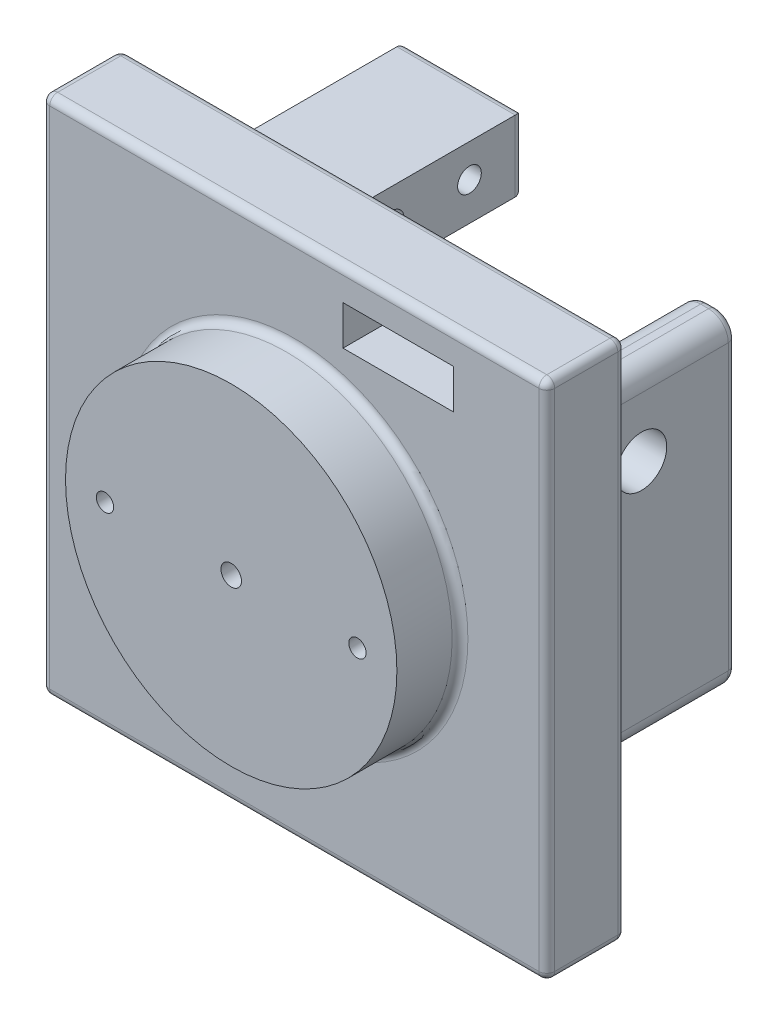
SolidWorks part; units mm, degrees
ref_plane "Front Plane" through (0, 0, 0) normal (0, 0, 1) x (1, 0, 0)
ref_plane "Top Plane" through (0, 0, 0) normal (0, 1, 0) x (1, 0, 0)
ref_plane "Right Plane" through (0, 0, 0) normal (1, 0, 0) x (0, 0, -1)
sketch "Sketch1" plane through (0, 0, 0) normal (0, 0, 1) x (1, 0, 0)
  circle A0 centre (0, 0) radius 21
  dimension "D1" = 42
extrude "Boss-Extrude1" add sketch "Sketch1" along normal blind 8
sketch "Sketch2" plane through (0, 0, 0) normal (0, 0, -1) x (-1, 0, 0)
  circle A0 centre (0, 0) radius 1.3
  dimension "D1" = 2.6
extrude "Cut-Extrude1" cut sketch "Sketch2" against normal through all both and the other way through all contours A0
sketch "Sketch4" plane through (0, 0, 0) normal (0, 0, -1) x (-1, 0, 0)
  circle A0 centre (16, 0) radius 1.1
  dimension "D1" = 16
  dimension "D3" = 2.2
  dimension "D2" = 0
sketch "Sketch5" plane through (0, 0, 0) normal (0, 0, -1) x (-1, 0, 0)
  circle A0 centre (-16, 0) radius 1.1
  dimension "D1" = 16
  dimension "D3" = 2.2
  dimension "D2" = 32
extrude "Cut-Extrude2" cut sketch "Sketch4" against normal blind 10
extrude "Cut-Extrude3" cut sketch "Sketch5" against normal blind 10
sketch "Sketch11" plane through (0, 0, 0) normal (0, 0, -1) x (-1, 0, 0)
  line L1 (-32, 33) -> (32, 33)
  line L2 (-32, 33) -> (-32, -33)
  line L3 (-32, -33) -> (32, -33)
  line L4 (32, 33) -> (32, -33)
  line L5 (-32, 33) -> (32, -33) construction
  line L6 (-32, -33) -> (32, 33) construction
  point P0 (0, 0)
  dimension "D1" = 64
  dimension "D2" = 66
extrude "Boss-Extrude3" add sketch "Sketch11" along normal blind 10
sketch "Sketch17" plane through (0, 0, 0) normal (0, 0, 1) x (1, 0, 0)
  circle A0 centre (0, 0) radius 1.3
  dimension "D1" = 2.6
extrude "Cut-Extrude8" cut sketch "Sketch17" against normal blind 10
sketch "Sketch12" plane through (0, 0, -10) normal (0, 0, -1) x (-1, 0, 0)
  line L0 (32, -33) -> (32, 33) construction
  line L1 (18, -29.5) -> (3, -29.5)
  line L2 (18, -29.5) -> (18, -20.5)
  line L3 (18, -20.5) -> (3, -20.5)
  line L4 (3, -29.5) -> (3, -20.5)
  line L5 (18, -29.5) -> (3, -20.5) construction
  line L6 (18, -20.5) -> (3, -29.5) construction
  line L7 (18, 20.5) -> (3, 20.5)
  line L8 (18, 20.5) -> (18, 29.5)
  line L9 (18, 29.5) -> (3, 29.5)
  line L10 (3, 20.5) -> (3, 29.5)
  line L11 (18, 20.5) -> (3, 29.5) construction
  line L12 (18, 29.5) -> (3, 20.5) construction
  line L13 (32, 33) -> (-32, 33) construction
  line L14 (-32, -33) -> (32, -33) construction
  point P0 (10.5, -25)
  point P5 (10.5, 25)
  dimension "D1" = 41
  dimension "D2" = 3.5
  dimension "D3" = 3.5
  dimension "D4" = 9
  dimension "D5" = 15
  dimension "D6" = 15
  dimension "D7" = 14
  dimension "D8" = 14
extrude "Boss-Extrude4" add sketch "Sketch12" along normal blind 22
sketch "Sketch13" plane through (-18, 0, 0) normal (-1, 0, 0) x (0, 0, 1)
  line L0 (-32, -29.5) -> (-32, -20.5) construction
  line L1 (-32, -29.5) -> (-10, -29.5) construction
  line L2 (-32, 29.5) -> (-10, 29.5) construction
  line L3 (-32, 20.5) -> (-32, 29.5) construction
  circle A0 centre (-25.2, -25.3) radius 1.5
  circle A1 centre (-15.4, -25.3) radius 1.5
  circle A2 centre (-25.2, 25.3) radius 1.5
  circle A3 centre (-15.4, 25.3) radius 1.5
  dimension "D2" = 3
  dimension "D3" = 3
  dimension "D7" = 3
  dimension "D8" = 3
  dimension "D1" = 9.8
  dimension "D4" = 4.2
  dimension "D5" = 4.2
  dimension "D6" = 6.8
  dimension "D9" = 9.8
  dimension "D10" = 4.2
  dimension "D11" = 6.8
  dimension "D12" = 4.2
extrude "Cut-Extrude4" cut sketch "Sketch13" against normal blind 21
sketch "Sketch14" plane through (0, 0, -10) normal (0, 0, -1) x (-1, 0, 0)
  line L0 (3, 20.5) -> (18, 20.5) construction
  line L1 (-24, 20.5) -> (-18, 20.5)
  line L2 (-24, 20.5) -> (-24, -20.5)
  line L3 (-24, -20.5) -> (-18, -20.5)
  line L4 (-18, 20.5) -> (-18, -20.5)
  line L5 (-24, 20.5) -> (-18, -20.5) construction
  line L6 (-24, -20.5) -> (-18, 20.5) construction
  line L7 (18, -20.5) -> (3, -20.5) construction
  point P0 (-21, 0)
  dimension "D1" = 36
  dimension "D2" = 0
  dimension "D3" = 0
  dimension "D4" = 6
extrude "Boss-Extrude5" add sketch "Sketch14" along normal blind 22
sketch "Sketch15" plane through (18, 0, 0) normal (-1, 0, 0) x (0, 0, 1)
  line L0 (-10, -20.5) -> (-10, 20.5) construction
  line L2 (-32, 20.5) -> (-10, 20.5) construction
  circle A0 centre (-20, 10.5) radius 3.2
  dimension "D1" = 10
  dimension "D3" = 6.4
  dimension "D2" = 10
extrude "Cut-Extrude6" cut sketch "Sketch15" against normal blind 22
fillet "Fillet12" radius 1 13 edges at (32, 0, 0) (21, 0, 0) (32, 33, -5) (0, 33, 0) (32, -33, -5) (0, -33, 0) (-32, -33, -5) (-32, 33, -5) (-32, 0, 0) (0, -33, -10) (32, 0, -10) (0, 33, -10) (-32, 0, -10)
fillet "Fillet13" radius 1 12 edges at (21, -20.5, -32) (24, 0, -32) (21, 20.5, -32) (18, 0, -32) (-10.5, 29.5, -32) (-18, 25, -32) (-10.5, 20.5, -32) (-3, 25, -32) (-10.5, -20.5, -32) (-18, -25, -32) (-10.5, -29.5, -32) (-3, -25, -32)
fillet "Fillet14" radius 2.5 12 edges at (18.2929, 20.2071, -31.7071) (18.2929, -20.2071, -31.7071) (23.7071, 20.2071, -31.7071) (23.7071, -20.2071, -31.7071) (21, 20.5, -10) (18, 0, -10) (18, 20.5, -20.5) (21, -20.5, -10) (18, -20.5, -20.5) (24, 0, -10) (24, 20.5, -20.5) (24, -20.5, -20.5)
sketch "Sketch16" plane through (0, 0, -10) normal (0, 0, -1) x (-1, 0, 0)
  line L0 (31, 32) -> (-31, 32) construction
  line L1 (-20.1709, 29) -> (-6.1709, 29)
  line L2 (-20.1709, 29) -> (-20.1709, 24)
  line L3 (-20.1709, 24) -> (-6.1709, 24)
  line L4 (-6.1709, 29) -> (-6.1709, 24)
  line L5 (-20.1709, 29) -> (-6.1709, 24) construction
  line L6 (-20.1709, 24) -> (-6.1709, 29) construction
  line L7 (-31, 32) -> (-31, -32) construction
  point P0 (-13.1709, 26.5)
  point P7 (-6.1709, 26.5)
  dimension "D1" = 3
  dimension "D2" = 14
  dimension "D3" = 5
  dimension "D4" = 10.8291
extrude "Cut-Extrude7" cut sketch "Sketch16" against normal blind 22
fillet "Fillet15" radius 2.5 6 edges at (-3, 25, -10) (-18, 25, -10) (-10.5, 29.5, -10) (-3, -25, -10) (-10.5, -29.5, -10) (-18, -25, -10)
sketch "Sketch18" plane through (0, 0, -10) normal (0, 0, -1) x (-1, 0, 0)
  circle A0 centre (0, 0) radius 2.75
  dimension "D1" = 5.5
extrude "Cut-Extrude9" cut sketch "Sketch18" against normal blind 3.1 contours A0
